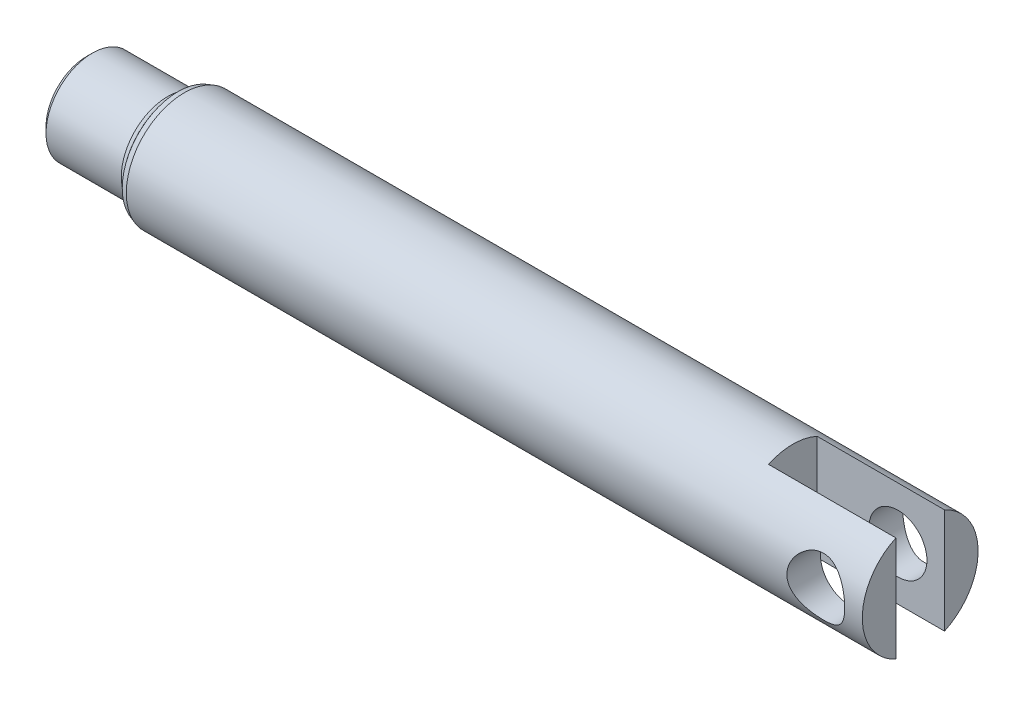
SolidWorks part; units mm, degrees
ref_plane "Front Plane" through (0, 0, 0) normal (0, 0, 1) x (1, 0, 0)
ref_plane "Top Plane" through (0, 0, 0) normal (0, 1, 0) x (1, 0, 0)
ref_plane "Right Plane" through (0, 0, 0) normal (1, 0, 0) x (0, 0, -1)
sketch "Sketch1" plane through (0, 0, 0) normal (0, 0, 1) x (1, 0, 0)
  line L0 (-18, 2) -> (-14.5, 2)
  line L1 (-14, 2.5) -> (18, 2.5)
  line L2 (18, 2.5) -> (18, 0)
  line L3 (18, 0) -> (-18, 0)
  line L4 (-18, 0) -> (-18, 2)
  arc A0 (-14.5, 2) -> (-14, 2.5) centre (-14.9795, 2.9795) ccw
  dimension "D1" = 2
  dimension "D2" = 32
  dimension "D3" = 2.5
  dimension "D4" = 0.5
  dimension "D5" = 3.5
revolve "Revolve1" add sketch "Sketch1" angle 360 about L3
sketch "Sketch2" plane through (18, 0, 0) normal (1, 0, 0) x (0, 0, -1)
  line L1 (-1.05, 2.912) -> (1.05, 2.912)
  line L2 (-1.05, 2.912) -> (-1.05, -2.912)
  line L3 (-1.05, -2.912) -> (1.05, -2.912)
  line L4 (1.05, 2.912) -> (1.05, -2.912)
  line L5 (-1.05, 2.912) -> (1.05, -2.912) construction
  line L6 (-1.05, -2.912) -> (1.05, 2.912) construction
  point P0 (0, 0)
  dimension "D1" = 2.1
extrude "Cut-Extrude1" cut sketch "Sketch2" against normal blind 5.5
sketch "Sketch3" plane through (0, 0, -1.05) normal (0, 0, 1) x (1, 0, 0)
  circle A0 centre (15.9912, 0) radius 1.25
  point P2 (15.9912, 0)
  dimension "D1" = 2.5
extrude "Cut-Extrude2" cut sketch "Sketch3" against normal through all both and the other way through all
chamfer "Chamfer1" distance 0.25 angle 45 1 edges at (-18, 0, -2)
chamfer "Chamfer2" distance 0.1 angle 45 1 edges at (-14, 0, -2.5) first distance on face at (-14.5, 0, -2)
